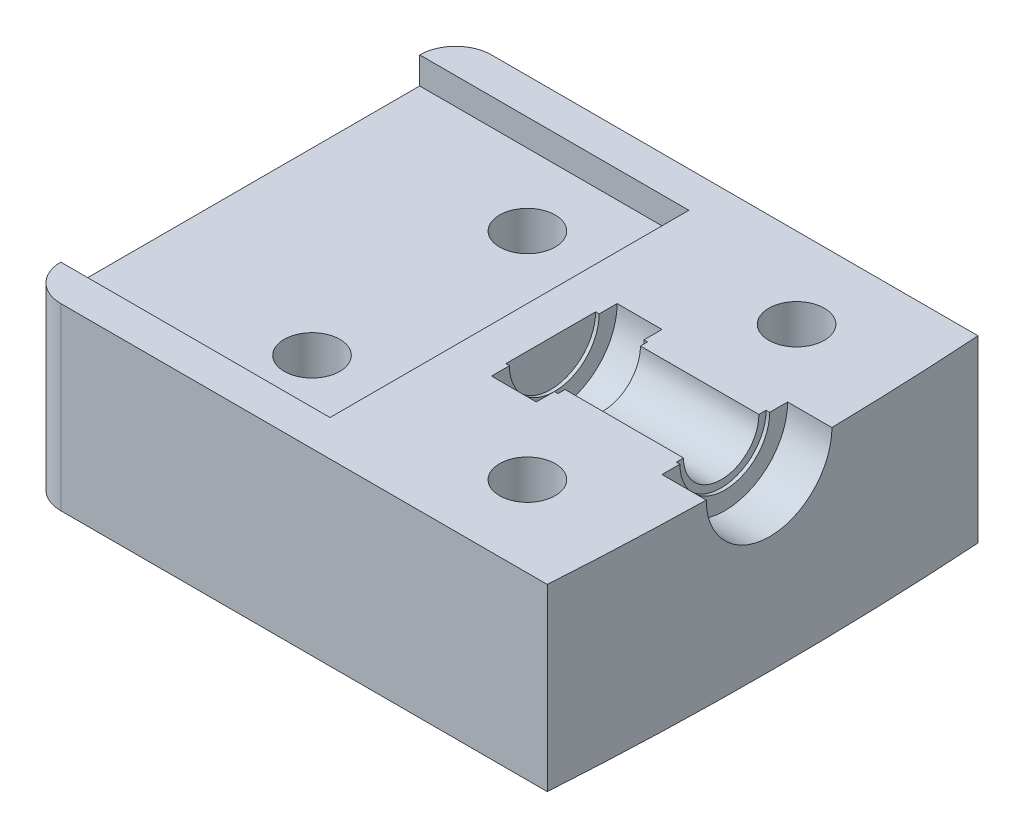
SolidWorks part; units mm, degrees
ref_plane "Front Plane" through (0, 0, 0) normal (0, 0, 1) x (1, 0, 0)
ref_plane "Top Plane" through (0, 0, 0) normal (0, 1, 0) x (1, 0, 0)
ref_plane "Right Plane" through (0, 0, 0) normal (1, 0, 0) x (0, 0, -1)
sketch "Sketch1" plane through (0, 0, 0) normal (0, 1, 0) x (1, 0, 0)
  line L0 (0, 0) -> (-180, 0) construction
  line L1 (0, -12) -> (-25, -12)
  line L2 (0, -12) -> (0, 12)
  line L3 (0, 12) -> (-25, 12)
  line L4 (-25, -12) -> (-25, 12)
  line L5 (-180, 0) -> (4.5, 0) construction
  line L6 (0, 12) -> (4.1093, 12)
  line L7 (0, -12) -> (4.1093, -12)
  line L8 (-180, 0) -> (5, 0) construction
  arc A0 (4.1093, -12) -> (4.1093, 12) centre (-180, 0) ccw
  circle A1 centre (-180, 0) radius 185 construction
  point P4 (0, 0)
  dimension "D4" = 184.5
  dimension "D5" = 185
  dimension "D1" = 25
  dimension "D2" = 24
  dimension "D3" = 180
extrude "Boss-Extrude1" add sketch "Sketch1" along normal blind 10 contours L4 L1 L2 L3 | L7 A0 L6 L2 region at (-12.5, 0, 0) region at (2.1865, 0, 0)
sketch "Sketch2" plane through (0, 10, 0) normal (0, 1, 0) x (1, 0, 0)
  line L1 (-25, -12) -> (-25, 12) construction
  line L2 (-25, 10) -> (-10, 10)
  line L3 (-25, 10) -> (-25, -10)
  line L4 (-25, -10) -> (-10, -10)
  line L5 (-10, 10) -> (-10, -10)
  point P0 (-25, 0)
  point P7 (-25, 0)
  dimension "D1" = 20
  dimension "D2" = 15
extrude "Cut-Extrude1" cut sketch "Sketch2" against normal blind 1.5
sketch "Sketch3" plane through (0, 10, 0) normal (0, 1, 0) x (1, 0, 0)
  line L0 (5, 0) -> (-7.5, 0) construction
  line L1 (0, 0) -> (-180, 0) construction
  dimension "D1" = 12.5
ref_plane "shaft" through (-7.5, 0, 0) normal (1, 0, 0) x (0, 0, -1)
sketch "Sketch4" plane through (-7.5, 0, 0) normal (1, 0, 0) x (0, 0, -1)
  line L0 (12, 10) -> (-12, 10) construction
  circle A0 centre (0, 10) radius 2.1
  dimension "D1" = 4.2
extrude "Cut-Extrude2" cut sketch "Sketch4" along normal through all
fillet "Fillet1" radius 2 2 edges at (-25, 5, -12) (-25, 5, 12)
sketch "Sketch5" plane through (-7.5, 0, 0) normal (1, 0, 0) x (0, 0, -1)
  line L0 (-2.1, 10) -> (2.1, 10) construction
  circle A0 centre (0, 10) radius 3.5
  dimension "D1" = 7
extrude "Cut-Extrude3" cut sketch "Sketch5" along normal blind 2.5
sketch "Sketch7" plane through (-7.5, 0, 0) normal (1, 0, 0) x (0, 0, -1)
  line L0 (-3.5, 10) -> (3.5, 10) construction
  circle A0 centre (0, 10) radius 2.5
  dimension "D1" = 5
extrude "Cut-Extrude4" cut sketch "Sketch7" against normal blind 0.2 and the other way blind 2.7
ref_plane "Plane2" through (0, 10, 0) normal (0, 1, 0) x (1, 0, 0)
sketch "Sketch8" plane through (0, 10, 0) normal (0, 1, 0) x (1, 0, 0)
  line L0 (0, 0) -> (4.5, 0) construction
  line L2 (2, 0) -> (4.5, 0)
  line L3 (2, 0) -> (2, 3.5)
  line L4 (2, 3.5) -> (4.5, 3.5)
  line L5 (4.5, 0) -> (4.5, 3.5)
  arc A0 (4.488, -2.1) -> (4.488, 2.1) centre (-180, 0) ccw construction
  dimension "D1" = 2.5
  dimension "D2" = 7
revolve "Cut-Revolve1" cut sketch "Sketch8" angle 360 about L0
sketch "Sketch9" plane through (2, 0, 0) normal (1, 0, 0) x (0, 0, -1)
  circle A0 centre (0, 10) radius 2.5
  dimension "D1" = 5
extrude "Cut-Extrude5" cut sketch "Sketch9" against normal blind 0.2
sketch "Sketch11" plane through (0, 8.5, 0) normal (0, 1, 0) x (1, 0, 0)
  circle A0 centre (-15, -6) radius 1.5 construction
  circle A1 centre (-15, 6) radius 1.5 construction
  circle A2 centre (-15, -6) radius 1.5 construction
  circle A3 centre (-15, 6) radius 1.5 construction
hole_wizard "Ø3.1 (3.1) Diameter Hole1" positions "Sketch12" profile "Sketch13" hole size "Ø3.1" standard "ISO" end condition through all
sketch "Sketch12" plane through (0, 8.5, 0) normal (0, 1, 0) x (1, 0, 0)
  point P0 (-15, 6)
  point P3 (-15, -6)
sketch "Sketch13" plane through (-15, 8.5, -6) normal (1, 0, 0) x (0, 0, 1)
  line L0 (0, 0) -> (0, 8.5)
  line L1 (0, 8.5) -> (1.55, 8.5)
  line L2 (1.55, 8.5) -> (1.55, 0)
  line L5 (1.55, 0) -> (0, 0)
  line L11 (0, -6.35) -> (0, 107.95) construction
  dimension "Thru Hole Dia." = 3.1
  dimension "Thru Hole Depth" = 8.5
sketch "Sketch14" plane through (0, 10, 0) normal (0, 1, 0) x (1, 0, 0)
  line L0 (-10, 0) -> (0, 0) construction
  line L1 (-10, -10) -> (-10, 10) construction
  line L2 (-1.5, 12) -> (-1.5, -12) construction
  line L3 (4.1093, 12) -> (-23, 12) construction
  line L4 (4.1093, -12) -> (-23, -12) construction
  point P7 (-1.5, -7.5)
  point P10 (-2.5, -8.516)
  point P13 (-1.5, 7.5)
  point P14 (0, 0)
  dimension "D1" = 8.5
  dimension "D2" = 15
hole_wizard "Ø3.1 (3.1) Diameter Hole2" positions "Sketch15" profile "Sketch16" hole size "Ø3.1" standard "ISO" end condition through all
sketch "Sketch15" plane through (0, 10, 0) normal (0, 1, 0) x (1, 0, 0)
  point P0 (-1.5, 7.5)
  point P3 (-1.5, -7.5)
sketch "Sketch16" plane through (-1.5, 10, -7.5) normal (1, 0, 0) x (0, 0, 1)
  line L0 (0, 0) -> (0, 10)
  line L1 (0, 10) -> (1.55, 10)
  line L2 (1.55, 10) -> (1.55, 0)
  line L5 (1.55, 0) -> (0, 0)
  line L11 (0, -6.35) -> (0, 107.95) construction
  dimension "Thru Hole Dia." = 3.1
  dimension "Thru Hole Depth" = 10
